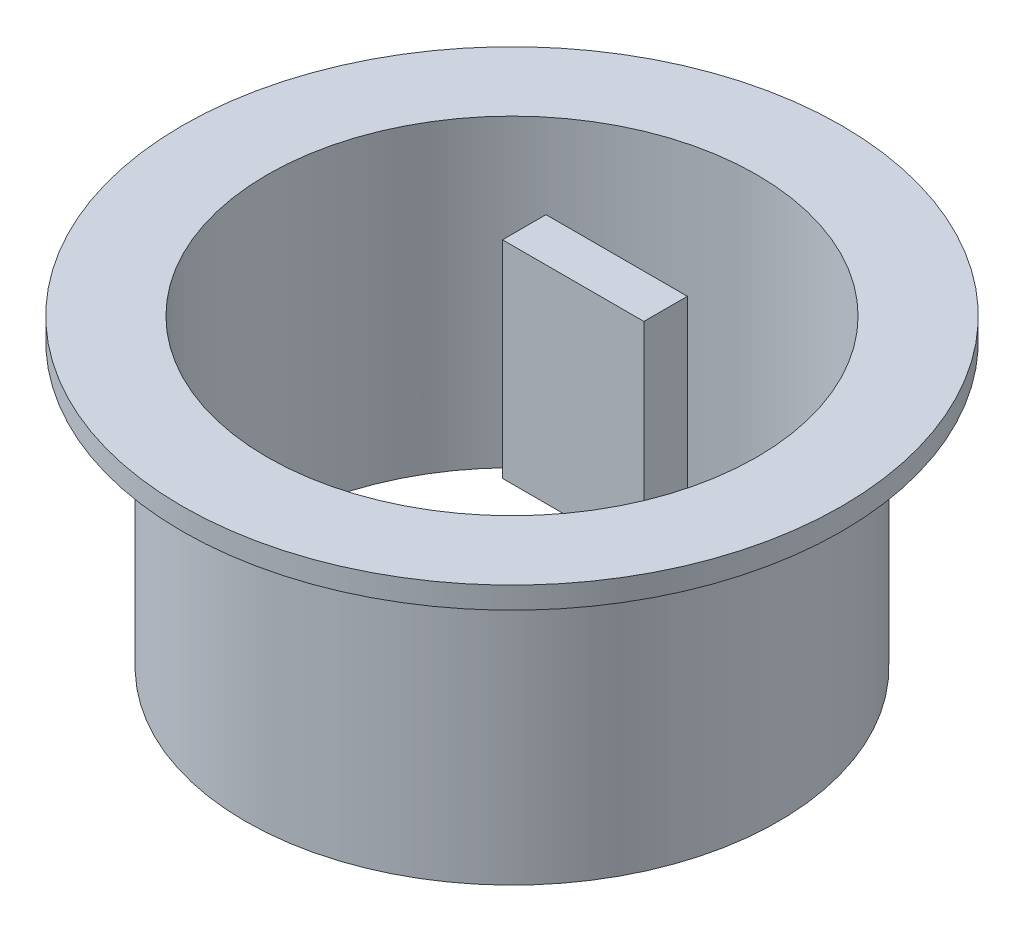
SolidWorks part; units mm, degrees
ref_plane "前视基准面" through (0, 0, 0) normal (0, 0, 1) x (1, 0, 0)
ref_plane "上视基准面" through (0, 0, 0) normal (0, 1, 0) x (1, 0, 0)
ref_plane "右视基准面" through (0, 0, 0) normal (1, 0, 0) x (0, 0, -1)
other "Configuration Table"
sketch "草图1" plane through (0, 0, 0) normal (0, 1, 0) x (1, 0, 0)
  circle A0 centre (0, 0) radius 60.625
  circle A1 centre (0, 0) radius 45
  dimension "D1" = 121.25
  dimension "D2" = 90
extrude "凸台-拉伸1" add sketch "草图1" along normal blind 4
sketch "草图8" plane through (0, 0, 0) normal (0, -1, 0) x (1, 0, 0)
  circle A0 centre (0, 0) radius 45 construction
  circle A1 centre (0, 0) radius 45
  circle A2 centre (0, 0) radius 49
  dimension "D1" = 4
extrude "凸台-拉伸3" add sketch "草图8" along normal blind 52
sketch "草图9" plane through (0, 0, 0) normal (1, 0, 0) x (0, 0, -1)
  line L0 (-45, 4) -> (-45, -52)
  line L1 (-46.75, -26) -> (-46.75, -34)
  line L2 (-46.75, -34) -> (-31.75, -34)
  line L3 (-31.75, -34) -> (-31.75, -26)
  line L4 (-31.75, -26) -> (-46.75, -26)
  line L5 (-31.75, -26) -> (-45, -24)
  line L6 (60.625, 4) -> (-60.625, 4) construction
  line L7 (11.25, -34) -> (19.25, -34)
  line L8 (11.25, -34) -> (11.25, 4)
  line L9 (11.25, 4) -> (19.25, 4)
  line L10 (19.25, -34) -> (19.25, 4)
  line L11 (11.25, -34) -> (19.25, 4) construction
  line L12 (11.25, 4) -> (19.25, -34) construction
  line L13 (-45, -52) -> (45, -52) construction
  point P6 (15.25, -15)
  point P16 (40.3234, -36.1126)
  point P20 (-46.75, -30)
  dimension "D1" = 18
  dimension "D2" = 8
  dimension "D3" = 11.25
  dimension "D4" = 43
  dimension "D5" = 15
  dimension "D6" = 8
  dimension "D7" = 18
extrude "凸台-拉伸4" add sketch "草图9" along normal mid plane 26 contours L4 L1 L2 L3
extrude "凸台-拉伸5" add sketch "草图9<3>" along normal mid plane 26 separate body contours L10 L9 L8 L7
sketch "草图9<3>" plane through (0, 0, 0) normal (1, 0, 0) x (0, 0, -1) same geometry as "草图9"
extrude "凸台-拉伸6" add sketch "草图9<8>" along normal mid plane 26 contours L4 L5 L0 region at (0, -25.3333, 40.5833)
sketch "草图9<8>" plane through (0, 0, 0) normal (1, 0, 0) x (0, 0, -1) same geometry as "草图9"
